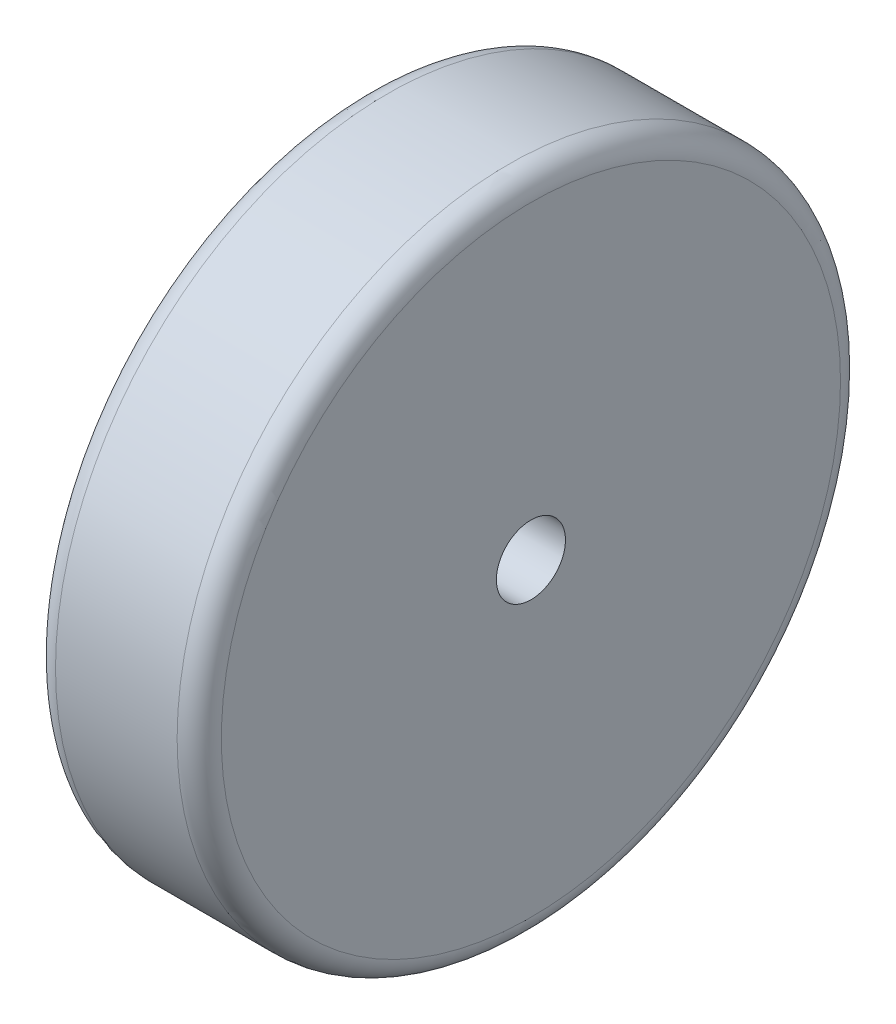
SolidWorks part; units mm, degrees
ref_plane "Front" through (0, 0, 0) normal (0, 0, 1) x (1, 0, 0)
ref_plane "Top" through (0, 0, 0) normal (0, 1, 0) x (1, 0, 0)
ref_plane "Right" through (0, 0, 0) normal (1, 0, 0) x (0, 0, -1)
sketch "Sketch1" plane through (0, 0, 0) normal (1, 0, 0) x (0, 0, -1)
  circle A0 centre (0, 0) radius 76.2
  circle A1 centre (0, 0) radius 7.9375
  dimension "D1" = 152.4
  dimension "D2" = 15.875
extrude "Boss-Extrude1" add sketch "Sketch1" along normal blind 38.1
fillet "Fillet1" radius 5.08 2 edges at (38.1, 0, -76.2) (0, 0, -76.2)
ref_plane "Bottom_Plane" through (0, 76.2, 0) normal (0, 1, 0) x (1, 0, 0)
ref_axis "Axis1" through (38.1, 0, 0) along (-1, 0, 0)
